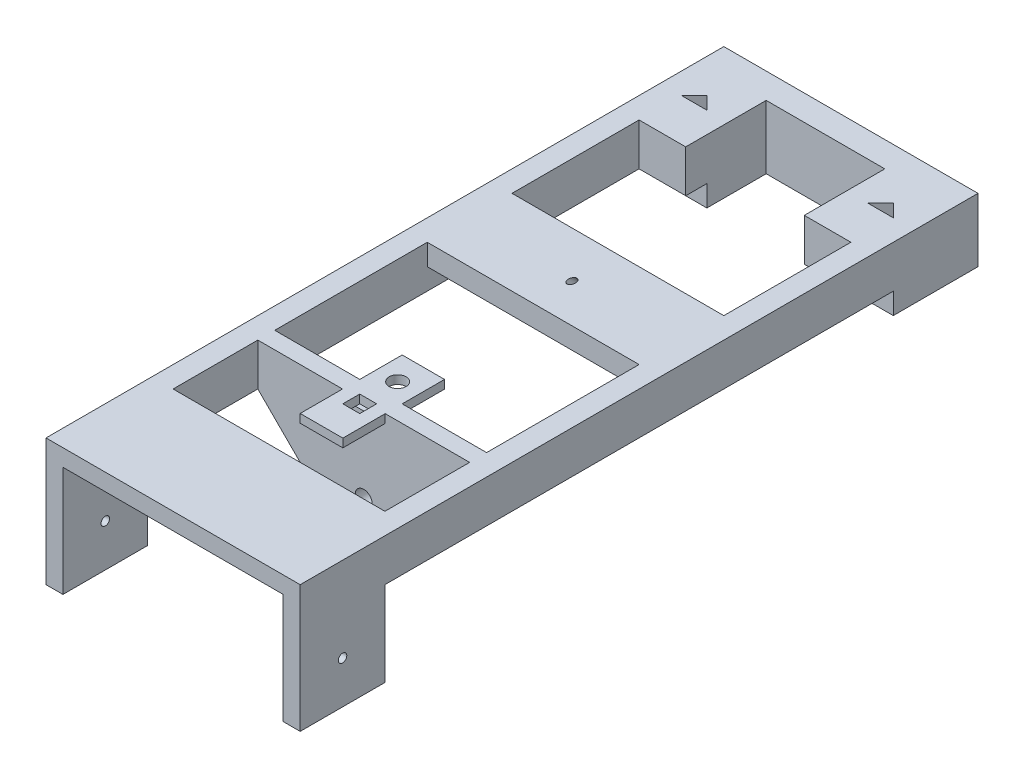
SolidWorks part; units mm, degrees
other "Markup1"
sketch "Sketch19" plane through (-15, 15, -40) normal (-0.0389, 0.0826, -0.9958) x (-0.519, -0.8533, -0.0505)
ref_plane "Front Plane" through (0, 0, 0) normal (0, 0, 1) x (1, 0, 0)
ref_plane "Top Plane" through (0, 0, 0) normal (0, 1, 0) x (1, 0, 0)
ref_plane "Right Plane" through (0, 0, 0) normal (1, 0, 0) x (0, 0, -1)
sketch "Sketch1" plane through (0, 0, 0) normal (0, 1, 0) x (1, 0, 0)
  line L1 (-15, 40) -> (15, 40)
  line L2 (-15, 40) -> (-15, -40)
  line L3 (-15, -40) -> (15, -40)
  line L4 (15, 40) -> (15, -40)
  line L5 (-15, 40) -> (15, -40) construction
  line L6 (-15, -40) -> (15, 40) construction
  point P0 (0, 0)
  dimension "D1" = 30
  dimension "D2" = 80
extrude "Boss-Extrude1" add sketch "Sketch1" along normal blind 5
sketch "Sketch2" plane through (15, 0, 0) normal (1, 0, 0) x (0, 0, -1)
  line L1 (-40, 0) -> (-30, 0)
  line L2 (-40, 0) -> (-40, -10)
  line L3 (-40, -10) -> (-30, -10)
  line L4 (-30, 0) -> (-30, -10)
  line L5 (40, 0) -> (30, 0)
  line L6 (40, 0) -> (40, -10)
  line L7 (40, -10) -> (30, -10)
  line L8 (30, 0) -> (30, -10)
  dimension "D1" = 10
  dimension "D2" = 10
  dimension "D3" = 10
  dimension "D4" = 10
extrude "Boss-Extrude2" add sketch "Sketch2" against normal blind 30
sketch "Sketch3" plane through (15, 0, 0) normal (1, 0, 0) x (0, 0, -1)
  line L0 (-40, 5) -> (-40, -10) construction
  line L2 (-40, -10) -> (-30, -10) construction
  line L15 (40, 5) -> (40, -10) construction
  line L16 (30, -10) -> (40, -10)
  line L17 (30, -10) -> (30, -2.5)
  line L18 (30, -2.5) -> (40, -2.5)
  line L19 (40, -10) -> (40, -2.5)
  circle A0 centre (-35, -5) radius 0.5
  dimension "D1" = 1
  dimension "D2" = 7.5
  dimension "D3" = 5
  dimension "D4" = 5
extrude "Cut-Extrude1" cut sketch "Sketch3" against normal through all both and the other way through all
sketch "Sketch4" plane through (0, 5, 0) normal (0, 1, 0) x (1, 0, 0)
  line L9 (-12.5, -27.5) -> (12.5, -27.5)
  line L10 (-12.5, -27.5) -> (-12.5, 27.5)
  line L11 (-12.5, 27.5) -> (12.5, 27.5)
  line L12 (12.5, -27.5) -> (12.5, 27.5)
  line L13 (-12.5, -27.5) -> (12.5, 27.5) construction
  line L14 (-12.5, 27.5) -> (12.5, -27.5) construction
  point P0 (0, 0)
  dimension "D1" = 55
  dimension "D2" = 25
extrude "Cut-Extrude2" cut sketch "Sketch4" against normal through all both and the other way through all
sketch "Sketch20" plane through (0, 5, 0) normal (0, 1, 0) x (1, 0, 0)
  line L0 (11, 34) -> (9.5, 32.5)
  line L1 (11, 34) -> (12.5, 32.5)
  line L2 (9.5, 32.5) -> (12.5, 32.5)
  line L3 (-11, 34) -> (-12.5, 32.5)
  line L4 (-11, 34) -> (-9.5, 32.5)
  line L5 (-12.5, 32.5) -> (-9.5, 32.5)
  line L6 (-15, 40) -> (-15, -40) construction
  line L7 (15, -40) -> (15, 40) construction
  line L9 (12.5, 27.5) -> (-12.5, 27.5) construction
  dimension "D1" = 3
  dimension "D2" = 3
  dimension "D3" = 5
  dimension "D4" = 5
  dimension "D5" = 2.5
  dimension "D6" = 2.5
extrude "Cut-Extrude4" cut sketch "Sketch20" against normal through all both and the other way through all
sketch "Sketch22" plane through (0, 0, 40) normal (0, 0, 1) x (1, 0, 0)
  line L0 (-15, -10) -> (15, -10) construction
  line L1 (-13, -10) -> (13, -10)
  line L2 (-13, -10) -> (-13, 3)
  line L3 (-13, 3) -> (13, 3)
  line L4 (13, -10) -> (13, 3)
  line L5 (-15, 5) -> (15, 5) construction
  line L6 (-15, 5) -> (-15, -10) construction
  line L7 (15, 5) -> (15, -10) construction
  dimension "D1" = 2
  dimension "D2" = 2
  dimension "D3" = 2
extrude "Cut-Extrude6" cut sketch "Sketch22" against normal up to surface (10 mm away) up to face at (0, -5, 30)
sketch "Sketch23" plane through (0, 5, 0) normal (0, 1, 0) x (1, 0, 0)
  line L0 (-12.5, 27.5) -> (-12.5, -27.5) construction
  line L5 (12.5, -27.5) -> (12.5, 27.5) construction
  line L7 (-12.5, -17.5) -> (12.5, -17.5)
  line L8 (-12.5, -17.5) -> (-12.5, -15.5)
  line L9 (-12.5, -15.5) -> (12.5, -15.5)
  line L10 (12.5, -17.5) -> (12.5, -15.5)
  line L11 (-12.5, -27.5) -> (12.5, -27.5) construction
  dimension "D1" = 2
  dimension "D4" = 10
extrude "Boss-Extrude3" add sketch "Sketch23" against normal blind 15
sketch "Sketch24" plane through (0, 0, 17.5) normal (0, 0, 1) x (1, 0, 0)
  line L0 (-12.5, -10) -> (12.5, -10) construction
  line L1 (-12.5, -10) -> (-12.5, 0) construction
  circle A0 centre (0, -5) radius 1
  dimension "D1" = 2
  dimension "D2" = 5
  dimension "D3" = 12.5
extrude "Cut-Extrude7" cut sketch "Sketch24" against normal up to surface (2 mm away) contours A0 up to face at (0, -1.6667, 15.5)
chamfer "Chamfer1" distance 10 angle 45 2 edges at (-12.5, -10, 16.5) (12.5, -10, 16.5)
sketch "Sketch25" plane through (0, 5, 0) normal (0, 1, 0) x (1, 0, 0)
  line L0 (2.5365, -15.5) -> (-2.4635, -15.5)
  line L7 (-2.4635, -15.5) -> (-2.4635, -10.5)
  line L8 (-2.4635, -10.5) -> (2.5365, -10.5)
  line L9 (2.5365, -15.5) -> (2.5365, -10.5)
  line L10 (-2.4635, -15.5) -> (2.5365, -10.5) construction
  line L11 (-2.4635, -10.5) -> (2.5365, -15.5) construction
  line L12 (-2.5, -17.5) -> (2.5365, -17.5)
  line L13 (-2.5, -17.5) -> (-2.5, -22.5)
  line L14 (-2.5, -22.5) -> (2.5365, -22.5)
  line L15 (2.5365, -17.5) -> (2.5365, -22.5)
  point P0 (0, 0)
  point P1 (0.0365, -13)
  dimension "D1" = 5
  dimension "D2" = 5
  dimension "D4" = 5
extrude "Boss-Extrude4" add sketch "Sketch25" against normal blind 1
sketch "Sketch26" plane through (0, 5, 0) normal (0, 1, 0) x (1, 0, 0)
  line L1 (-2.4635, -15.5) -> (-12.5, -15.5) construction
  circle A0 centre (0, -13.5) radius 1
  dimension "D1" = 2
  dimension "D2" = 2
extrude "Cut-Extrude8" cut sketch "Sketch26" against normal through all both and the other way through all
sketch "Sketch27" plane through (0, 5, 0) normal (0, 1, 0) x (1, 0, 0)
  line L1 (-0.9711, -19) -> (1.0289, -19)
  line L2 (-0.9711, -19) -> (-0.9711, -17)
  line L3 (-0.9711, -17) -> (1.0289, -17)
  line L4 (1.0289, -19) -> (1.0289, -17)
  line L5 (-0.9711, -19) -> (1.0289, -17) construction
  line L6 (-0.9711, -17) -> (1.0289, -19) construction
  circle A0 centre (0, -13.5) radius 1 construction
  point P0 (0.0289, -18)
  dimension "D3" = 4.5
  dimension "D1" = 2
  dimension "D2" = 2
extrude "Cut-Extrude9" cut sketch "Sketch27" against normal blind 1
sketch "Sketch28" plane through (0, 5, 0) normal (0, 1, 0) x (1, 0, 0)
  line L2 (12.5, 27.5) -> (-12.5, 27.5) construction
  line L3 (-7, 27.5) -> (7, 27.5)
  line L4 (-7, 27.5) -> (-7, 37)
  line L5 (-7, 37) -> (7, 37)
  line L6 (7, 27.5) -> (7, 37)
  line L7 (-15, 40) -> (-15, -40) construction
  line L8 (15, -40) -> (15, 40) construction
  line L9 (15, 40) -> (-15, 40) construction
  dimension "D1" = 8
  dimension "D2" = 8
  dimension "D3" = 3
extrude "Cut-Extrude11" cut sketch "Sketch28" against normal through all both and the other way through all
sketch "Sketch29" plane through (0, 5, 0) normal (0, 1, 0) x (1, 0, 0)
  line L0 (-12.5, 27.5) -> (-12.5, -15.5) construction
  line L1 (-12.5, 2.5) -> (12.5, 2.5)
  line L2 (-12.5, 2.5) -> (-12.5, 12.5)
  line L3 (-12.5, 12.5) -> (12.5, 12.5)
  line L4 (12.5, 2.5) -> (12.5, 12.5)
  line L5 (12.5, -15.5) -> (12.5, 27.5) construction
  line L6 (-7, 27.5) -> (-12.5, 27.5) construction
  dimension "D1" = 10
  dimension "D2" = 15
extrude "Boss-Extrude5" add sketch "Sketch29" against normal blind 2.5
ref_plane "Plane1" through (0, -17.5, -17.5) normal (0, -0.7071, -0.7071) x (-1, 0, 0)
sketch "Sketch30" plane through (0, -17.5, -17.5) normal (0, -0.7071, -0.7071) x (-1, 0, 0)
  line L0 (12.5, 3.5355) -> (-12.5, 3.5355) construction
  circle A0 centre (0, 8.5355) radius 0.415
  dimension "D2" = 0.83
  dimension "D1" = 5
extrude "Cut-Extrude12" cut sketch "Sketch30" against normal through all both and the other way through all
equation "\"w\"=3.9113"
